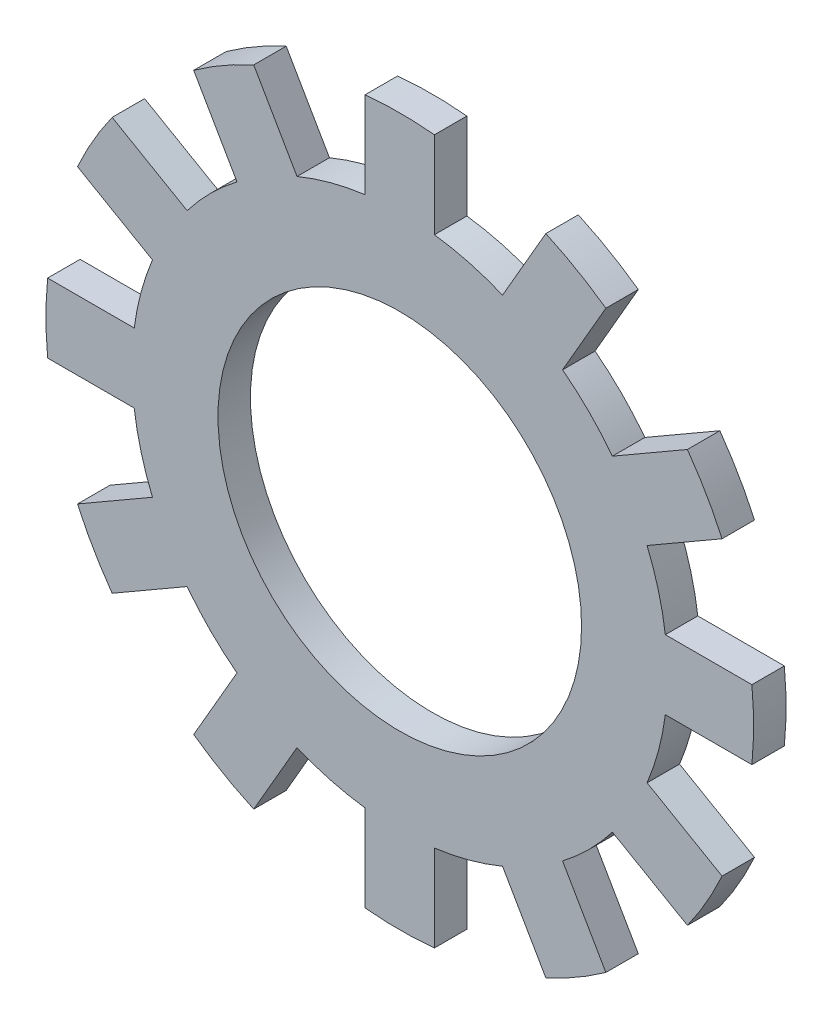
SolidWorks part; units mm, degrees
ref_plane "Front Plane" through (0, 0, 0) normal (0, 0, 1) x (1, 0, 0)
ref_plane "Top Plane" through (0, 0, 0) normal (0, 1, 0) x (1, 0, 0)
ref_plane "Right Plane" through (0, 0, 0) normal (1, 0, 0) x (0, 0, -1)
sketch "Sketch1" plane through (0, 0, 0) normal (0, 0, 1) x (1, 0, 0)
  circle A0 centre (0, 0) radius 2.725 construction
  circle A1 centre (0, 0) radius 1.4
  circle A2 centre (0, 0) radius 2.0625
  dimension "D1" = 4.125
extrude "Extrude1" add sketch "Sketch1" along normal blind 0.25
sketch "Sketch2" plane through (0, 0, 0) normal (0, 0, 1) x (1, 0, 0)
  line L0 (0, 0) -> (0, 2.725) construction
  line L1 (0, 0) -> (0.7053, 2.6321) construction
  line L2 (0, 0) -> (-0.7053, 2.6321) construction
  line L3 (-0.5338, 1.9922) -> (0, 1.9922) construction
  line L4 (-0.2669, 2.7119) -> (-0.2669, 2.0452)
  line L5 (0.2669, 2.7119) -> (0.2669, 2.0452)
  line L6 (-0.2669, 2.0452) -> (0.2669, 2.0452)
  circle A0 centre (0, 0) radius 2.0625 construction
  circle A1 centre (0, 0) radius 2.0625 construction
  circle A2 centre (0, 0) radius 2.725 construction
  arc A3 (0.2669, 2.7119) -> (-0.2669, 2.7119) centre (0, 0) ccw
  dimension "D2" = 15
  dimension "D3" = 15
extrude "Extrude2" add sketch "Sketch2" along normal up to surface (0.25 mm away) up to face at (2.0625, 0, 0.25)
pattern_circular "CirPattern1" count 12 over 360 of "Extrude2"
sketch "Sketch3" plane through (0, 0, 0) normal (0, 0, 1) x (1, 0, 0)
  line L0 (-0.3187, 2.7063) -> (-0.3187, 2.0377)
  line L1 (0.3187, 2.7063) -> (0.3187, 2.0377)
  line L2 (0, 0) -> (0, 2.725) construction
  line L3 (0, 0) -> (0.8421, 2.5916) construction
  line L4 (0, 0) -> (-0.8421, 2.5916) construction
  line L5 (-0.6373, 1.9616) -> (0, 1.9616) construction
  line L6 (-0.3187, 2.0377) -> (0.3187, 2.0377)
  circle A0 centre (0, 0) radius 2.725 construction
  circle A1 centre (0, 0) radius 2.0625 construction
  circle A2 centre (0, 0) radius 2.0625 construction
  arc A3 (0.3187, 2.7063) -> (-0.3187, 2.7063) centre (0, 0) ccw
  dimension "D2" = 18
  dimension "D3" = 18
extrude "Extrude3" [suppressed] add sketch "Sketch3" along normal up to surface (0.25 mm away) up to face at (0, 0, 0.25)
pattern_circular "CirPattern2" [suppressed] count 10 over 360 of bodies 104
equation "\"D1@Sketch1\" =  ( \"B@Sketch1\" + \"A@Sketch1\" )  / 2"
